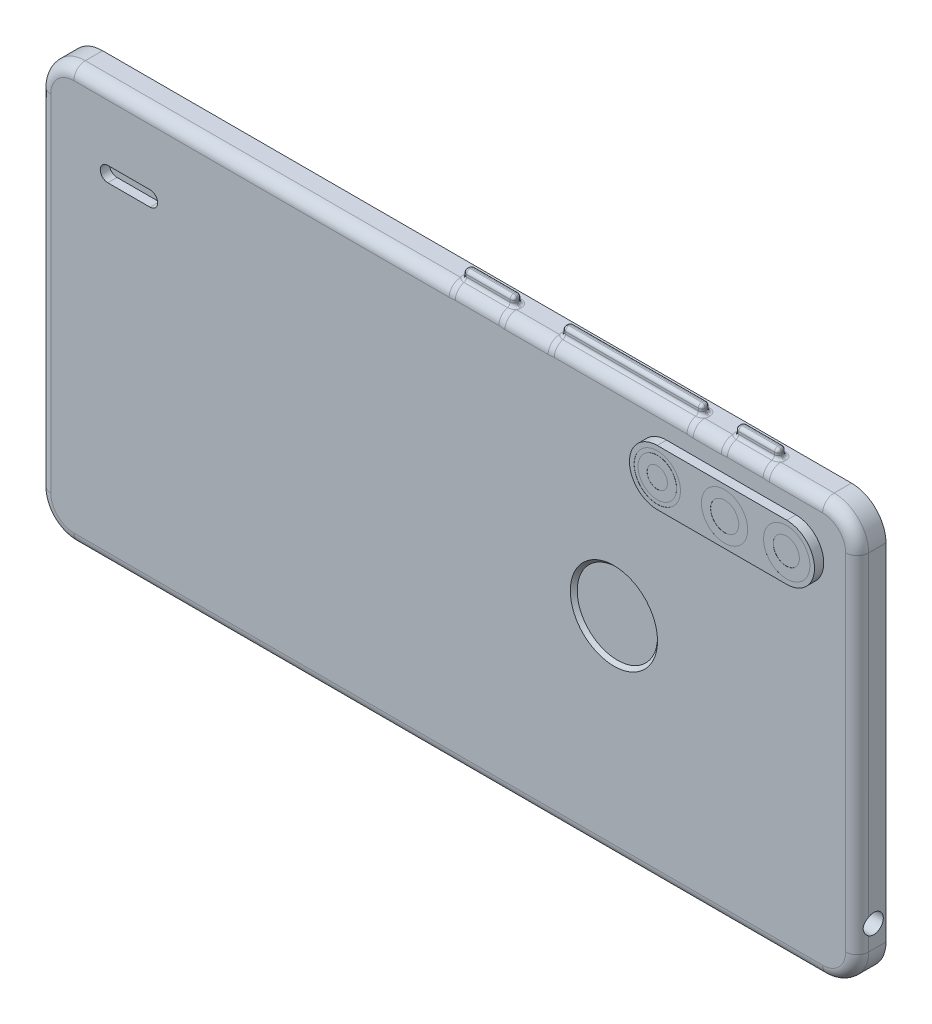
SolidWorks part; units mm, degrees
ref_plane "Front Plane" through (0, 0, 0) normal (0, 0, 1) x (1, 0, 0)
ref_plane "Top Plane" through (0, 0, 0) normal (0, 1, 0) x (1, 0, 0)
ref_plane "Right Plane" through (0, 0, 0) normal (1, 0, 0) x (0, 0, -1)
sketch "Sketch1" plane through (0, 0, 0) normal (0, 0, 1) x (1, 0, 0)
  line L1 (-63.1535, 22.8492) -> (101.9465, 22.8492)
  line L2 (-70.7735, 15.2292) -> (-70.7735, -60.9708)
  line L3 (-63.1535, -68.5908) -> (101.9465, -68.5908)
  line L4 (109.5665, 15.2292) -> (109.5665, -60.9708)
  arc A0 (101.9465, 22.8492) -> (109.5665, 15.2292) centre (101.9465, 15.2292) cw
  arc A1 (101.9465, -68.5908) -> (109.5665, -60.9708) centre (101.9465, -60.9708) ccw
  arc A2 (-70.7735, -60.9708) -> (-63.1535, -68.5908) centre (-63.1535, -60.9708) ccw
  arc A3 (-63.1535, 22.8492) -> (-70.7735, 15.2292) centre (-63.1535, 15.2292) ccw
  dimension "D1" = 7.62
  dimension "D2" = 76.2
  dimension "D3" = 165.1
extrude "Boss-Extrude1" add sketch "Sketch1" along normal blind 6.35 contours L1 A0 L4 A1 L3 A2 L2 A3
sketch "Sketch3" plane through (0, 22.8492, 0) normal (0, 1, 0) x (1, 0, 0)
  line L1 (89.5991, -2.0455) -> (80.1889, -2.0455)
  line L2 (89.5991, -2.0455) -> (89.5991, -3.8634)
  line L3 (89.5991, -3.8634) -> (80.1889, -3.8634)
  line L4 (80.1889, -2.0455) -> (80.1889, -3.8634)
  line L5 (72.8104, -2.0455) -> (42.0132, -2.0455)
  line L6 (72.8104, -2.0455) -> (72.8104, -3.8634)
  line L7 (72.8104, -3.8634) -> (42.0132, -3.8634)
  line L8 (42.0132, -2.0455) -> (42.0132, -3.8634)
  line L9 (31.3197, -2.0455) -> (20.1985, -2.0455)
  line L10 (31.3197, -2.0455) -> (31.3197, -3.8634)
  line L11 (31.3197, -3.8634) -> (20.1985, -3.8634)
  line L12 (20.1985, -2.0455) -> (20.1985, -3.8634)
extrude "Boss-Extrude2" add sketch "Sketch3" along normal blind 2.032
fillet "Fillet2" radius 0.762 36 edges at (31.3197, 22.8492, 2.9544) (25.7591, 22.8492, 2.0455) (20.1985, 22.8492, 2.9544) (25.7591, 22.8492, 3.8634) (31.3197, 24.8812, 2.9544) (20.1985, 24.8812, 2.9544) (25.7591, 24.8812, 3.8634) (31.3197, 23.8652, 3.8634) (20.1985, 23.8652, 3.8634) (20.1985, 23.8652, 2.0455) (31.3197, 23.8652, 2.0455) (72.8104, 22.8492, 2.9544) (57.4118, 22.8492, 2.0455) (42.0132, 22.8492, 2.9544) (57.4118, 22.8492, 3.8634) (72.8104, 24.8812, 2.9544) (42.0132, 24.8812, 2.9544) (57.4118, 24.8812, 3.8634) (72.8104, 23.8652, 3.8634) (42.0132, 23.8652, 3.8634) (42.0132, 23.8652, 2.0455) (72.8104, 23.8652, 2.0455) (89.5991, 22.8492, 2.9544) (84.894, 22.8492, 2.0455) (80.1889, 22.8492, 2.9544) (84.894, 22.8492, 3.8634) (89.5991, 24.8812, 2.9544) (80.1889, 24.8812, 2.9544) (84.894, 24.8812, 3.8634) (89.5991, 23.8652, 3.8634) (80.1889, 23.8652, 3.8634) (80.1889, 23.8652, 2.0455) (89.5991, 23.8652, 2.0455) (84.894, 24.8812, 2.0455) (57.4118, 24.8812, 2.0455) (25.7591, 24.8812, 2.0455)
sketch "Sketch4" plane through (0, -68.5908, 0) normal (0, -1, 0) x (1, 0, 0)
  line L1 (86.0071, 4.3294) -> (69.5032, 4.3294)
  line L2 (86.7691, 3.5674) -> (86.7691, 3.4262)
  line L3 (86.0071, 2.6642) -> (69.5032, 2.6642)
  line L4 (68.7412, 3.5674) -> (68.7412, 3.4262)
  line L12 (86.0071, 2.4102) -> (69.5032, 2.4102)
  line L13 (68.4872, 3.5674) -> (68.4872, 3.4262)
  line L14 (86.0071, 4.5834) -> (69.5032, 4.5834)
  line L15 (87.0231, 3.5674) -> (87.0231, 3.4262)
  line L16 (-60.6135, 2.54) -> (99.4065, 2.54)
  line L17 (99.4065, 2.54) -> (99.4065, 3.81)
  line L18 (99.4065, 3.81) -> (-60.6135, 3.81)
  line L19 (-60.6135, 3.81) -> (-60.6135, 2.54)
  line L21 (99.4065, 2.54) -> (99.4065, 3.81)
  line L23 (-60.6135, 3.81) -> (-60.6135, 2.54)
  arc A0 (69.5032, 2.6642) -> (68.7412, 3.4262) centre (69.5032, 3.4262) cw
  arc A1 (86.0071, 4.3294) -> (86.7691, 3.5674) centre (86.0071, 3.5674) cw
  arc A2 (86.7691, 3.4262) -> (86.0071, 2.6642) centre (86.0071, 3.4262) cw
  arc A3 (69.5032, 4.3294) -> (68.7412, 3.5674) centre (69.5032, 3.5674) ccw
  circle A4 centre (71.1135, 3.4262) radius 0.3559
  arc A5 (69.5032, 2.4102) -> (68.4872, 3.4262) centre (69.5032, 3.4262) cw
  arc A6 (69.5032, 4.5834) -> (68.4872, 3.5674) centre (69.5032, 3.5674) ccw
  arc A7 (86.0071, 4.5834) -> (87.0231, 3.5674) centre (86.0071, 3.5674) cw
  arc A8 (87.0231, 3.4262) -> (86.0071, 2.4102) centre (86.0071, 3.4262) cw
  dimension "D1" = 0.762
  dimension "D2" = 2.54
  dimension "D3" = 0.254
sketch "Sketch5" plane through (0, -68.5908, 0) normal (0, -1, 0) x (1, 0, 0)
  circle A0 centre (71.1135, 3.4262) radius 0.3672
extrude "Cut-Extrude2" cut sketch "Sketch5" against normal blind 2.54
extrude "Cut-Extrude3" cut sketch "Sketch4" against normal blind 1.27 contours L1 A3 L4 A0 L3 A2 L2 A1 | L14 A6 L13 A5 L12 A8 L15 A7
fillet "Fillet3" radius 2.54 8 edges at (19.3965, 22.8492, 6.35) (107.3347, 20.6174, 6.35) (109.5665, -22.8708, 6.35) (107.3347, -66.3589, 6.35) (19.3965, -68.5908, 6.35) (-68.5416, -66.3589, 6.35) (-70.7735, -22.8708, 6.35) (-68.5416, 20.6174, 6.35)
sketch "Sketch6" plane through (0, 0, 0) normal (0, 0, -1) x (-1, 0, 0)
  line L4 (-106.0105, -26.9656) -> (-106.0105, -60.9708)
  line L5 (-109.5665, 15.2292) -> (-109.5665, -60.9708) construction
  line L6 (63.1535, 22.8492) -> (-101.9465, 22.8492) construction
  line L7 (70.7735, 15.2292) -> (70.7735, -60.9708) construction
  line L8 (63.1535, 19.2932) -> (-101.9465, 19.2932)
  line L9 (-106.0105, 15.2292) -> (-106.0105, -60.9708)
  line L10 (-101.9465, -65.0348) -> (63.1535, -65.0348)
  line L11 (67.2175, -60.9708) -> (67.2175, 15.2292)
  line L12 (63.1535, 19.2932) -> (-101.9465, 19.2932)
  line L13 (-106.0105, 15.2292) -> (-106.0105, -18.776)
  line L14 (-101.9465, -65.0348) -> (63.1535, -65.0348)
  line L15 (67.2175, -60.9708) -> (67.2175, 15.2292)
  line L16 (63.1535, -68.5908) -> (-101.9465, -68.5908) construction
  line L17 (-109.5665, 15.2292) -> (-109.5665, -60.9708)
  line L18 (63.1535, 22.8492) -> (-101.9465, 22.8492)
  line L19 (70.7735, 15.2292) -> (70.7735, -60.9708)
  line L20 (63.1535, -68.5908) -> (-101.9465, -68.5908)
  arc A4 (-106.0105, -26.9656) -> (-106.0105, -18.776) centre (-106.0105, -22.8708) ccw
  arc A5 (-109.5665, -60.9708) -> (-101.9465, -68.5908) centre (-101.9465, -60.9708) ccw construction
  arc A6 (-101.9465, 22.8492) -> (-109.5665, 15.2292) centre (-101.9465, 15.2292) ccw construction
  arc A7 (70.7735, 15.2292) -> (63.1535, 22.8492) centre (63.1535, 15.2292) ccw construction
  arc A8 (67.2175, 15.2292) -> (63.1535, 19.2932) centre (63.1535, 15.2292) ccw
  arc A9 (-101.9465, 19.2932) -> (-106.0105, 15.2292) centre (-101.9465, 15.2292) ccw
  arc A10 (-106.0105, -60.9708) -> (-101.9465, -65.0348) centre (-101.9465, -60.9708) ccw
  arc A11 (63.1535, -65.0348) -> (67.2175, -60.9708) centre (63.1535, -60.9708) ccw
  arc A12 (67.2175, 15.2292) -> (63.1535, 19.2932) centre (63.1535, 15.2292) ccw
  arc A13 (-101.9465, 19.2932) -> (-106.0105, 15.2292) centre (-101.9465, 15.2292) ccw
  arc A14 (-106.0105, -60.9708) -> (-101.9465, -65.0348) centre (-101.9465, -60.9708) ccw
  arc A15 (63.1535, -65.0348) -> (67.2175, -60.9708) centre (63.1535, -60.9708) ccw
  arc A16 (63.1535, -68.5908) -> (70.7735, -60.9708) centre (63.1535, -60.9708) ccw construction
  arc A17 (-109.5665, -60.9708) -> (-101.9465, -68.5908) centre (-101.9465, -60.9708) ccw
  arc A18 (-101.9465, 22.8492) -> (-109.5665, 15.2292) centre (-101.9465, 15.2292) ccw
  arc A19 (70.7735, 15.2292) -> (63.1535, 22.8492) centre (63.1535, 15.2292) ccw
  arc A20 (63.1535, -68.5908) -> (70.7735, -60.9708) centre (63.1535, -60.9708) ccw
  dimension "D1" = 3.556
sketch "Sketch7" plane through (0, 0, 6.35) normal (0, 0, 1) x (1, 0, 0)
  line L0 (96.0587, 10.8761) -> (67.5173, 10.8761) construction
  line L1 (96.0587, 4.7488) -> (67.5173, 4.7488)
  line L2 (96.0587, 17.0034) -> (67.5173, 17.0034)
  arc A0 (96.0587, 4.7488) -> (96.0587, 17.0034) centre (96.0587, 10.8761) ccw
  arc A1 (67.5173, 17.0034) -> (67.5173, 4.7488) centre (67.5173, 10.8761) ccw
  point P2 (81.788, 10.8761)
extrude "Boss-Extrude3" add sketch "Sketch7" along normal blind 2.032
sketch "Sketch8" plane through (0, 0, 6.35) normal (0, 0, 1) x (1, 0, 0)
  circle A0 centre (55.9291, -22.3396) radius 9.6134
extrude "Cut-Extrude4" cut sketch "Sketch8" against normal blind 0.762 draft 45
sketch "Sketch9" plane through (0, 0, 6.35) normal (0, 0, 1) x (1, 0, 0)
  line L0 (-55.6628, 6.2158) -> (-46.331, 6.2158) construction
  line L1 (-55.6628, 7.8763) -> (-46.331, 7.8763)
  line L2 (-55.6628, 4.5554) -> (-46.331, 4.5554)
  arc A0 (-55.6628, 7.8763) -> (-55.6628, 4.5554) centre (-55.6628, 6.2158) ccw
  arc A1 (-46.331, 4.5554) -> (-46.331, 7.8763) centre (-46.331, 6.2158) ccw
  point P2 (-50.9969, 6.2158)
extrude "Cut-Extrude5" cut sketch "Sketch9" against normal blind 2.032
extrude "Cut-Extrude6" cut sketch "Sketch6" against normal blind 0.0025
sketch "Sketch10" plane through (0, 0, 8.382) normal (0, 0, 1) x (1, 0, 0)
  circle A0 centre (96.0587, 10.8761) radius 5.1082
  circle A1 centre (67.5173, 10.8761) radius 5.1082
  circle A2 centre (82.3542, 10.8761) radius 5.1082
  arc A4 (96.0587, 4.7488) -> (96.0587, 17.0034) centre (96.0587, 10.8761) ccw construction
  point P14 (102.186, 10.8761)
  dimension "D1" = 6.1273
extrude "Cut-Extrude7" cut sketch "Sketch10" against normal blind 0.0025
sketch "Sketch12" plane through (0, 0, 0) normal (0, 0, -1) x (-1, 0, 0)
  line L0 (-106.0105, -26.9656) -> (-106.0105, -60.9708) construction
  line L1 (-106.0105, 15.2292) -> (-106.0105, -18.776) construction
  line L2 (63.1535, 19.2932) -> (-101.9465, 19.2932) construction
  line L3 (-101.9465, -65.0348) -> (63.1535, -65.0348) construction
  line L4 (-106.0105, -26.9656) -> (-106.0105, -60.9708)
  line L5 (-106.0105, 15.2292) -> (-106.0105, -18.776)
  line L6 (63.1535, 19.2932) -> (-101.9465, 19.2932)
  line L7 (-101.9465, -65.0348) -> (63.1535, -65.0348)
  arc A0 (-106.0105, -60.9708) -> (-101.9465, -65.0348) centre (-101.9465, -60.9708) ccw construction
  arc A1 (-106.0105, -26.9656) -> (-106.0105, -18.776) centre (-106.0105, -22.8708) ccw construction
  arc A2 (-101.9465, 19.2932) -> (-106.0105, 15.2292) centre (-101.9465, 15.2292) ccw construction
  arc A3 (63.1535, -65.0348) -> (67.2175, -60.9708) centre (63.1535, -60.9708) ccw construction
  arc A4 (-106.0105, -60.9708) -> (-101.9465, -65.0348) centre (-101.9465, -60.9708) ccw
  arc A5 (-106.0105, -26.9656) -> (-106.0105, -18.776) centre (-106.0105, -22.8708) ccw
  arc A6 (-101.9465, 19.2932) -> (-106.0105, 15.2292) centre (-101.9465, 15.2292) ccw
  arc A7 (63.1535, -65.0348) -> (67.2175, -60.9708) centre (63.1535, -60.9708) ccw
  arc M9 (-106.0105, -18.776) -> (-106.0105, -26.9656) centre (-106.0105, -22.8708) cw
  line M10 (-106.0105, -26.9656) -> (-106.0105, -60.9708)
  arc M11 (-106.0105, -60.9708) -> (-101.9465, -65.0348) centre (-101.9465, -60.9708) ccw
  line M12 (-101.9465, -65.0348) -> (63.1535, -65.0348)
  arc M13 (63.1535, -65.0348) -> (67.2175, -60.9708) centre (63.1535, -60.9708) ccw
  line M14 (67.2175, -60.9708) -> (67.2175, 15.2292)
  arc M15 (67.2175, 15.2292) -> (63.1535, 19.2932) centre (63.1535, 15.2292) ccw
  line M16 (63.1535, 19.2932) -> (-101.9465, 19.2932)
  arc M17 (-101.9465, 19.2932) -> (-106.0105, 15.2292) centre (-101.9465, 15.2292) ccw
  line M18 (-106.0105, 15.2292) -> (-106.0105, -18.776)
extrude "Cut-Extrude10" cut sketch "Sketch12" against normal blind 0.0254 and the other way through all contours M18 M9 M10 M11 M12 M13 M14 M15 M16 M17 region at (19.2431, -22.8708, 0)
sketch "Sketch14" plane through (0, 0, 8.382) normal (0, 0, 1) x (1, 0, 0)
  circle A0 centre (67.5173, 10.8761) radius 2.2477
  circle A1 centre (67.5173, 10.8761) radius 4.2508
  circle A2 centre (82.3849, 10.8761) radius 3.1106
  circle A3 centre (95.9668, 11.0685) radius 2.8826
  circle M2 centre (67.5173, 10.8761) radius 5.1082
extrude "Cut-Extrude11" cut sketch "Sketch14" against normal blind 0.0254 contours A0 region at (67.5173, 10.8761, 8.382)
extrude "Cut-Extrude13" cut sketch "Sketch14<4>" against normal blind 0.0254 contours A2 | A3 | A1 M2 region at (82.3849, 10.8761, 8.382) region at (95.9668, 11.0685, 8.382) region at (62.5536, 10.8761, 8.382)
sketch "Sketch14<4>" plane through (0, 0, 8.382) normal (0, 0, 1) x (1, 0, 0) same geometry as "Sketch14"
sketch "Sketch15" plane through (0, 0, 0.0025) normal (0, 0, -1) x (-1, 0, 0)
  circle A0 centre (-106.0105, -22.8708) radius 3.1475
extrude "Cut-Extrude14" cut sketch "Sketch15" against normal blind 0.0254
sketch "Sketch16" plane through (-70.7735, 0, 0) normal (-1, 0, 0) x (0, 0, 1)
  line L0 (1.5003, -16.106) -> (1.5003, -22.7664) construction
  line L1 (2.6073, -16.106) -> (2.6073, -22.7664)
  line L2 (0.3934, -16.106) -> (0.3934, -22.7664)
  arc A0 (2.6073, -16.106) -> (0.3934, -16.106) centre (1.5003, -16.106) ccw
  arc A1 (0.3934, -22.7664) -> (2.6073, -22.7664) centre (1.5003, -22.7664) ccw
  circle A2 centre (1.5003, -50.0092) radius 0.8795
  point P2 (1.5003, -19.4362)
extrude "Cut-Extrude15" cut sketch "Sketch16" against normal blind 6.35
sketch "Sketch17" plane through (109.5665, 0, 0) normal (1, 0, 0) x (0, 0, -1)
  circle A0 centre (-2.7063, -56.1017) radius 2.1153
extrude "Cut-Extrude16" cut sketch "Sketch17" against normal blind 20.32 draft 1
